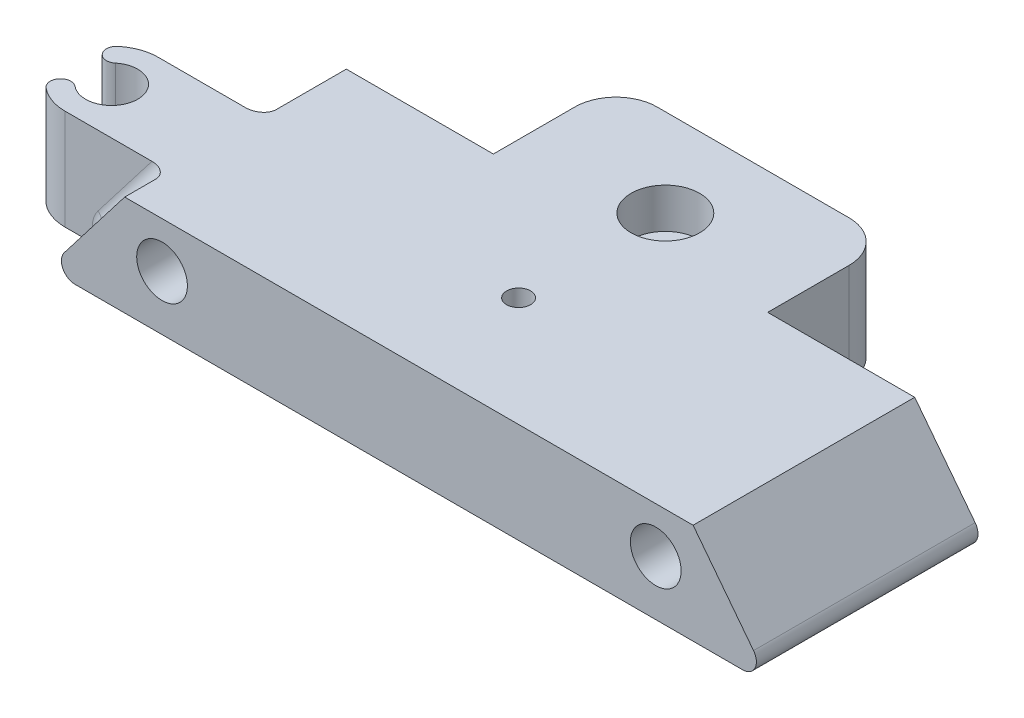
SolidWorks part; units mm, degrees
ref_plane "Front Plane" through (0, 0, 0) normal (0, 0, 1) x (1, 0, 0)
ref_plane "Top Plane" through (0, 0, 0) normal (0, 1, 0) x (1, 0, 0)
ref_plane "Right Plane" through (0, 0, 0) normal (1, 0, 0) x (0, 0, -1)
sketch "Sketch1" plane through (0, 0, 0) normal (0, 1, 0) x (1, 0, 0)
  line L0 (-10.0004, -2.54) -> (10.0004, -2.54) construction
  line L1 (-10.0004, -2.54) -> (10.0004, -2.54)
  line L2 (16, -2.54) -> (20, -2.54) construction
  line L3 (16, -2.54) -> (20, -2.54)
  line L5 (26.925, -8.15) -> (26.925, 0) construction
  line L7 (-26.925, 0) -> (-26.925, -8.15) construction
  line L8 (-20, -2.54) -> (-16, -2.54) construction
  line L9 (-20, -2.54) -> (-16, -2.54)
  line L10 (26.925, -8.15) -> (26.925, 0)
  line L11 (-26.925, 0) -> (-26.925, -8.15)
  line L12 (1.8552, -13.973) -> (2.6903, -2.3287)
  line L13 (-2.6903, -2.3287) -> (-1.8552, -13.973)
  line L14 (1.8552, -13.973) -> (2.6903, -2.3287)
  line L15 (-2.6903, -2.3287) -> (-1.8552, -13.973)
  circle A0 centre (0, -10.7) radius 1 construction
  circle A1 centre (0, -10.7) radius 1
  arc A4 (2.8496, -1.8547) -> (2.6903, -2.3287) centre (3.6877, -2.4002) ccw
  arc A5 (2.8496, -1.8547) -> (-2.8496, -1.8547) centre (0, 0) ccw
  arc A6 (-2.6903, -2.3287) -> (-2.8496, -1.8547) centre (-3.6877, -2.4002) ccw
  arc A7 (-1.8552, -13.973) -> (1.8552, -13.973) centre (0, -13.84) ccw
  arc A8 (2.8496, -1.8547) -> (2.6903, -2.3287) centre (3.6877, -2.4002) ccw
  arc A9 (2.8496, -1.8547) -> (-2.8496, -1.8547) centre (0, 0) ccw
  arc A10 (-2.6903, -2.3287) -> (-2.8496, -1.8547) centre (-3.6877, -2.4002) ccw
  arc A11 (-1.8552, -13.973) -> (1.8552, -13.973) centre (0, -13.84) ccw
  dimension "D1" = 0
ref_plane "Plane1" through (0, 4.425, 0) normal (0, -1, 0) x (-1, 0, 0)
ref_plane "Plane2" through (0, -2.9, 0) normal (0, -1, 0) x (-1, 0, 0)
ref_plane "Plane3" through (0, 0, 2.54) normal (0, 0, 1) x (1, 0, 0)
sketch "Sketch2" plane through (0, 0, 2.54) normal (0, 0, 1) x (1, 0, 0)
  circle A0 centre (-18, 1.1) radius 2 construction
  circle A1 centre (18, 1.1) radius 2 construction
  circle A2 centre (-18, 1.1) radius 2
  circle A3 centre (18, 1.1) radius 2
sketch "Sketch4" plane through (0, 0, 0) normal (0, 1, 0) x (1, 0, 0)
  line L0 (26.925, -8.15) -> (26.925, 0) construction
  line L1 (-26.925, -2.54) -> (-10.0004, -2.54)
  line L2 (-26.925, -2.54) -> (-26.925, -18.7)
  line L3 (-26.925, -18.7) -> (26.925, -18.7)
  line L4 (26.925, -2.54) -> (26.925, -18.7)
  line L5 (-10.0004, -2.54) -> (10.0004, -2.54) construction
  line L6 (-26.925, 0) -> (-26.925, -8.15) construction
  line L7 (10.0004, -2.54) -> (10.0004, 6.4)
  line L8 (10.0004, 6.4) -> (-10.0004, 6.4)
  line L9 (-10.0004, 6.4) -> (-10.0004, -2.54)
  line L10 (10.0004, -2.54) -> (26.925, -2.54)
  arc A0 (-1.8552, -13.973) -> (1.8552, -13.973) centre (0, -13.84) ccw construction
  arc A1 (-1.8552, -13.973) -> (1.8552, -13.973) centre (0, -13.84) ccw construction
  arc A2 (2.8496, -1.8547) -> (-2.8496, -1.8547) centre (0, 0) ccw construction
  point P13 (0, -15.7)
  point P17 (0, 3.4)
  dimension "D1" = 3
  dimension "D2" = 3
extrude "Boss-Extrude1" add sketch "Sketch4" along normal up to surface (4.425 mm away) and the other way up to surface (2.9 mm away) up to plane "Plane1" other way up to plane "Plane2"
sketch "Sketch5" plane through (0, 0, 0) normal (0, 1, 0) x (1, 0, 0)
  line L0 (1.8552, -13.973) -> (2.6903, -2.3287) construction
  line L1 (-2.6903, -2.3287) -> (-1.8552, -13.973) construction
  line L2 (1.8552, -13.973) -> (2.6903, -2.3287) construction
  line L3 (-2.6903, -2.3287) -> (-1.8552, -13.973) construction
  line L4 (2.0049, -13.9838) -> (2.8399, -2.3394)
  line L5 (-2.8399, -2.3394) -> (-2.0049, -13.9838)
  arc A0 (-1.8552, -13.973) -> (1.8552, -13.973) centre (0, -13.84) ccw construction
  arc A1 (-2.6903, -2.3287) -> (-2.8496, -1.8547) centre (-3.6877, -2.4002) ccw construction
  arc A2 (2.8496, -1.8547) -> (2.6903, -2.3287) centre (3.6877, -2.4002) ccw construction
  arc A3 (2.8496, -1.8547) -> (-2.8496, -1.8547) centre (0, 0) ccw construction
  arc A4 (-1.8552, -13.973) -> (1.8552, -13.973) centre (0, -13.84) ccw construction
  arc A5 (-2.6903, -2.3287) -> (-2.8496, -1.8547) centre (-3.6877, -2.4002) ccw construction
  arc A6 (2.8496, -1.8547) -> (2.6903, -2.3287) centre (3.6877, -2.4002) ccw construction
  arc A7 (2.8496, -1.8547) -> (-2.8496, -1.8547) centre (0, 0) ccw construction
  arc A8 (2.9753, -1.9365) -> (2.8399, -2.3394) centre (3.6877, -2.4002) ccw
  arc A9 (2.9753, -1.9365) -> (-2.9753, -1.9365) centre (0, 0) ccw
  arc A10 (-2.8399, -2.3394) -> (-2.9753, -1.9365) centre (-3.6877, -2.4002) ccw
  arc A11 (-2.0049, -13.9838) -> (2.0049, -13.9838) centre (0, -13.84) ccw
  dimension "D1" = 0.15
extrude "Cut-Extrude1" cut sketch "Sketch5" against normal through all
sketch "Sketch6" plane through (0, 4.425, 0) normal (0, 1, 0) x (1, 0, 0)
  circle A0 centre (0, 0) radius 1.3
  dimension "D1" = 2.6
extrude "Cut-Extrude2" cut sketch "Sketch6" against normal through all
sketch "Sketch7" plane through (0, 4.425, 0) normal (0, 1, 0) x (1, 0, 0)
  circle A0 centre (0, 0) radius 2.5
  dimension "D1" = 5
extrude "Cut-Extrude3" cut sketch "Sketch7" against normal offset from surface (2.925 mm away) 1.5 up to face at (0, 0, 1.3)
sketch "Sketch8" plane through (0, 0, 0) normal (0, -1, 0) x (1, 0, 0)
  circle A0 centre (0, 10.7) radius 0.875
  dimension "D1" = 1.75
extrude "Cut-Extrude4" cut sketch "Sketch8" against normal through all
sketch "Sketch9" plane through (0, 0, 2.54) normal (0, 0, -1) x (-1, 0, 0)
  circle A0 centre (18, 1.1) radius 1.85
  circle A1 centre (-18, 1.1) radius 1.85
  dimension "D1" = 3.7
extrude "Cut-Extrude5" cut sketch "Sketch9" against normal through all
sketch "Sketch10" plane through (0, 0, 18.7) normal (0, 0, 1) x (1, 0, 0)
  line L0 (-22.1244, 3.0179) -> (-20.7551, 4.7934) construction
  line L1 (20.7551, 4.7934) -> (22.1244, 3.0179) construction
  line L2 (-22.1244, 3.0179) -> (-20.7551, 4.7934)
  line L3 (20.7551, 4.7934) -> (22.1244, 3.0179)
sketch "Sketch11" plane through (0, 0, 18.7) normal (0, 0, 1) x (1, 0, 0)
  line L0 (-20.7235, 4.425) -> (-26.3726, -2.9)
  line L1 (-22.1244, 3.0179) -> (-20.7551, 4.7934) construction
  line L2 (-26.925, -2.9) -> (26.925, -2.9) construction
  line L3 (-26.925, 4.425) -> (-26.925, -2.9) construction
  line L4 (26.925, 4.425) -> (-26.925, 4.425) construction
  line L5 (-26.925, -2.9) -> (-26.3726, -2.9)
  line L6 (-26.925, 4.425) -> (-26.925, -2.9)
  line L7 (-20.7235, 4.425) -> (-26.925, 4.425)
  line L8 (0, 5.6937) -> (0, -5.6937) construction
  line L9 (20.7235, 4.425) -> (26.925, 4.425)
  line L10 (26.925, 4.425) -> (26.925, -2.9)
  line L11 (26.925, -2.9) -> (26.3726, -2.9)
  line L12 (20.7235, 4.425) -> (26.3726, -2.9)
  point P10 (0, 0)
  dimension "D1" = 0.25
extrude "Cut-Extrude6" cut sketch "Sketch11" against normal through all
fillet "Fillet1" radius 1 2 edges at (-26.3726, -2.9, 10.62) (26.3726, -2.9, 10.62)
fillet "Fillet2" radius 3 2 edges at (-10.0004, 0.7625, -6.4) (10.0004, 0.7625, -6.4)
sketch "Sketch12" plane through (0, 4.425, 0) normal (0, 1, 0) x (1, 0, 0)
  line L0 (-22.1244, -8.15) -> (-20.7551, -8.15) construction
  line L1 (-22.1244, -8.15) -> (-20.7551, -8.15)
  line L3 (-23.1478, -10) -> (-20.7235, -10)
  line L4 (-26.6269, -8.15) -> (-25.2, -35) construction
  line L5 (-26.6269, -8.15) -> (-25.2, -35)
sketch "Sketch13" plane through (0, 4.425, 0) normal (0, 1, 0) x (1, 0, 0)
  line L0 (-20.7235, -2.54) -> (-20.7235, -18.7) construction
  line L1 (-20.7235, -2.54) -> (-20.7235, -18.7)
  line L2 (-20.7235, -8.65) -> (-26.6003, -8.65)
  line L3 (-26.6269, -8.15) -> (-25.2, -35) construction
  line L4 (-22.1244, -8.15) -> (-20.7551, -8.15) construction
  line L5 (-28.3223, -12.05) -> (-37.9123, -12.05) construction
  line L6 (-33.1173, -10.75) -> (-33.1173, -13.35) construction
  line L7 (-28.3223, -10.75) -> (-37.9123, -10.75) construction
  line L8 (-28.3223, -13.35) -> (-37.9123, -13.35) construction
  circle A0 centre (-28.3223, -12.05) radius 1.9
  circle A1 centre (-28.3223, -12.05) radius 3.4
  circle A2 centre (-30.0016, -10) radius 0.75
  circle A3 centre (-30.0016, -14.1) radius 0.75
  point P15 (-33.1173, -12.05)
  point P16 (-33.1173, -12.05)
  point P21 (-33.1173, -10.75)
  point P22 (-33.1173, -13.35)
  dimension "D2" = 3.8
  dimension "D1" = 0.5
  dimension "D4" = 2.6
  dimension "D3" = 1.5
sketch "Sketch14" plane through (0, 4.425, 0) normal (0, 1, 0) x (1, 0, 0)
  line L0 (-20.7235, -8.65) -> (-26.6003, -8.65) construction
  line L1 (-20.7235, -2.54) -> (-20.7235, -18.7) construction
  line L2 (-20.7235, -8.65) -> (-28.3223, -8.65)
  line L3 (-20.7235, -8.65) -> (-20.7235, -15.45)
  line L4 (-20.7235, -15.45) -> (-28.3223, -15.45)
  arc A0 (-28.3223, -8.65) -> (-30.4769, -9.4198) centre (-28.3223, -12.05) ccw
  circle A1 centre (-28.3223, -12.05) radius 3.4
  arc A2 (-30.4769, -14.6802) -> (-28.3223, -15.45) centre (-28.3223, -12.05) ccw
  circle A3 centre (-28.3223, -12.05) radius 1.9
  arc A4 (-29.5263, -13.5198) -> (-29.5263, -10.5802) centre (-28.3223, -12.05) ccw
  circle A5 centre (-30.0016, -14.1) radius 0.75
  arc A6 (-29.5263, -13.5198) -> (-30.4769, -14.6802) centre (-30.0016, -14.1) ccw
  circle A7 centre (-30.0016, -10) radius 0.75
  arc A8 (-30.4769, -9.4198) -> (-29.5263, -10.5802) centre (-30.0016, -10) ccw
  dimension "D1" = 0
  dimension "D2" = 0
  dimension "D3" = 0
  dimension "D4" = 0
extrude "Boss-Extrude2" add sketch "Sketch14" against normal through all
fillet "Fillet3" radius 1 4 edges at (-25.236, -2.3412, 8.65) (-25.236, -2.3412, 15.45) (-22.927, 1.5678, 8.65) (-22.927, 1.5678, 15.45)
